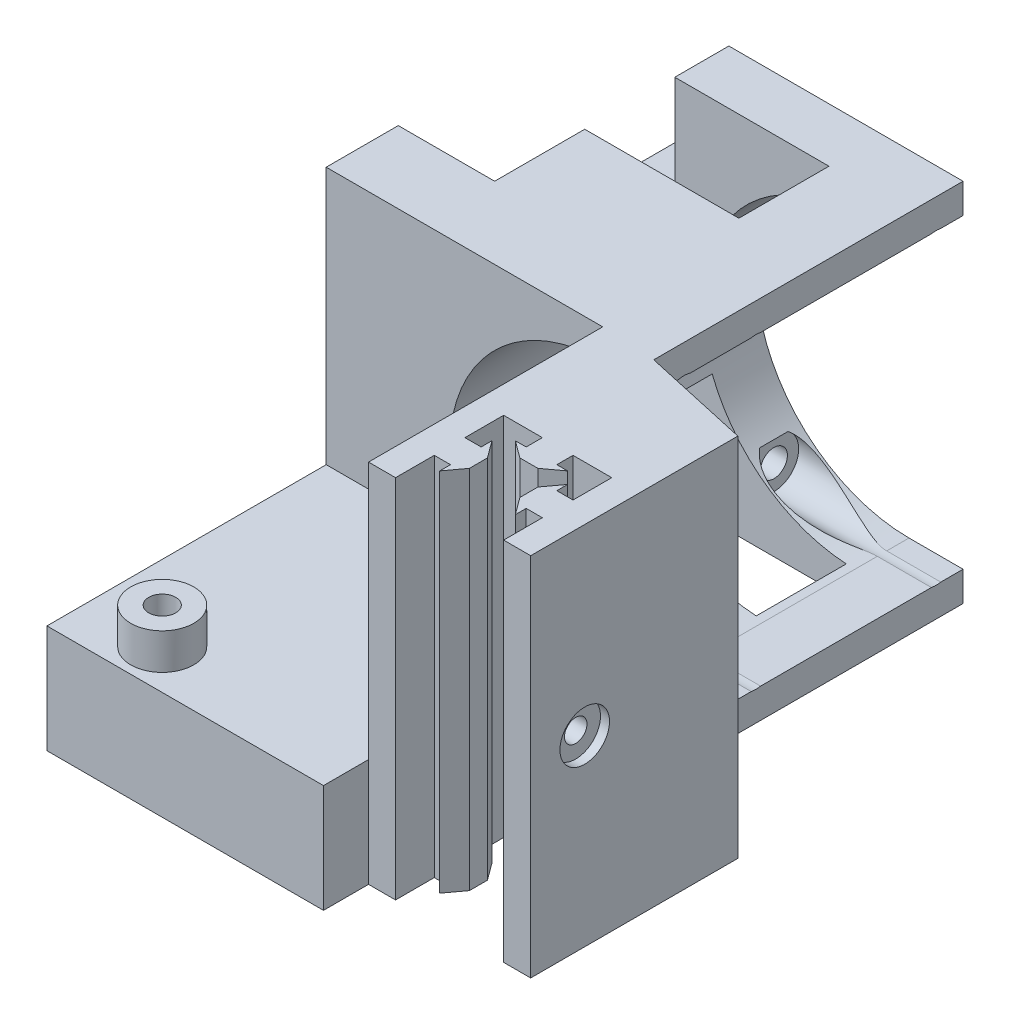
SolidWorks part; units mm, degrees
ref_plane "Plan de face" through (0, 0, 0) normal (0, 0, 1) x (1, 0, 0)
ref_plane "Plan de dessus" through (0, 0, 0) normal (0, 1, 0) x (1, 0, 0)
ref_plane "Plan de droite" through (0, 0, 0) normal (1, 0, 0) x (0, 0, -1)
ref_plane "Plan milieu" through (0, 0, -54) normal (0, 0, 1) x (1, 0, 0)
ref_axis "Axe1" through (0, 19.3307, 0) along (0, -1, 0)
ref_axis "Axe2" through (23.7847, 0, 0) along (-1, 0, 0)
ref_axis "Axe3" through (0, 0, -92.2336) along (0, 0, 1)
sketch "Esquisse8" plane through (0, 0, 0) normal (0, 1, 0) x (1, 0, 0)
  line L0 (-6, 1.7) -> (-4.2, 1.7)
  line L1 (0, -17.9979) -> (0, 17.9979) construction
  line L2 (-4.2, 1.7) -> (-4.2, 2.9)
  line L3 (-4.2, 2.9) -> (-2.8, 1)
  line L4 (-2.8, 1) -> (-2.8, -1)
  line L5 (-2.8, -1) -> (-4.2, -2.9)
  line L6 (-4.2, -2.9) -> (-4.2, -1.7)
  line L7 (-4.2, -1.7) -> (-6, -1.7)
  line L8 (-6, -1.7) -> (-6, -9)
  line L9 (-6, -9) -> (-9, -9)
  line L10 (-9, -9) -> (-9, 9)
  line L11 (-9, 9) -> (-6, 9)
  line L12 (-6, 9) -> (-6, 1.7)
  line L16 (23.7847, 0) -> (-17.9556, 0) construction
  point P14 (-2.8, 0)
  dimension "D1" = 1.8
  dimension "D2" = 3.2
  dimension "D3" = 18
  dimension "D4" = 2
  dimension "D5" = 1.2
  dimension "D7" = 3
  dimension "D8" = 3.4
  dimension "D9" = 6
extrude "Boss.-Extru.6" add sketch "Esquisse8" along normal mid plane 40.6 separate body
pattern_circular "Répétition circulaire3" count 3 every 90 about axis through (0, 19.3307, 0) along (0, -1, 0) of bodies 117
sketch "Esquisse9" plane through (0, 20.3, 0) normal (0, 1, 0) x (1, 0, 0)
  line L0 (9, -9) -> (9, 9) construction
  line L1 (-9, -9) -> (9, -9)
  line L2 (-9, -9) -> (-9, -6)
  line L3 (-9, -6) -> (9, -6)
  line L4 (9, -9) -> (9, -6)
  dimension "D1" = 3
extrude "Enlèv. mat.-Extru.1" cut sketch "Esquisse9" against normal through all
sketch "Esquisse10" plane through (0, 0, -9) normal (0, 0, -1) x (-1, 0, 0)
  line L0 (6, -20.3) -> (9, -20.3) construction
  line L1 (9, 20.3) -> (3, 20.3)
  line L2 (9, 20.3) -> (9, -20.3)
  line L3 (9, -20.3) -> (3, -20.3)
  line L4 (3, 20.3) -> (3, -20.3)
  line L5 (-9, -20.3) -> (9, -20.3) construction
  dimension "D1" = 6
extrude "Boss.-Extru.7" add sketch "Esquisse10" along normal up to surface (45 mm away) up to plane "Plan milieu"
sketch "Esquisse13" plane through (0, -20.3, 0) normal (0, -1, 0) x (-1, 0, 0)
  line L0 (9, 21) -> (-9, 17)
  line L1 (9, 54) -> (9, -6) construction
  line L2 (9, 21) -> (9, 9)
  line L3 (9, 9) -> (-9, 9)
  line L4 (-9, 6) -> (-9, 9) construction
  line L5 (-9, 17) -> (-9, 9)
  line L6 (9, 54) -> (9, -6) construction
  dimension "D1" = 12
  dimension "D2" = 8
extrude "Boss.-Extru.8" add sketch "Esquisse13" against normal up to surface (40.6 mm away) up to face at (-1.9333, 20.3, -7.6208)
sketch "Esquisse15" plane through (9, 0, 0) normal (1, 0, 0) x (0, 0, -1)
  line L0 (-6, -20.3) -> (-6, 20.3) construction
  line L2 (0, 19.3307) -> (0, -16.6651) construction
  circle A0 centre (0, 0) radius 1.25
  point P2 (-6, 0)
  dimension "D1" = 2.5
extrude "Enlèv. mat.-Extru.3" cut sketch "Esquisse15" against normal up to next
sketch "Esquisse19" plane through (9, 0, 0) normal (1, 0, 0) x (0, 0, -1)
  circle A0 centre (0, 0) radius 2.75
  circle A1 centre (0, 0) radius 1.25 construction
  dimension "D1" = 5.5
extrude "Enlèv. mat.-Extru.5" cut sketch "Esquisse19" against normal blind 1
sketch "Esquisse20" plane through (-9, 0, 0) normal (-1, 0, 0) x (0, 0, 1)
  line L0 (6, -20.3) -> (-54, -20.3) construction
  line L1 (-20, -20.3) -> (11, -20.3)
  line L2 (-20, -20.3) -> (-20, -8.3)
  line L3 (-20, -8.3) -> (11, -8.3)
  line L4 (11, -20.3) -> (11, -8.3)
  line L5 (6, -20.3) -> (6, 20.3) construction
  dimension "D1" = 31
  dimension "D2" = 12
  dimension "D3" = 5
extrude "Boss.-Extru.9" add sketch "Esquisse20" along normal blind 30.7
sketch "Esquisse21" plane through (0, -8.3, 0) normal (0, 1, 0) x (1, 0, 0)
  line L0 (-39.7, -11) -> (-39.7, 20) construction
  line L1 (-39.7, -11) -> (-9, -11) construction
  line L2 (-9, -6) -> (-9, 20) construction
  line L3 (-39.7, 20) -> (-9, 20) construction
  circle A0 centre (-31.3, -6.6) radius 3.5
  circle A1 centre (-13, 16) radius 3.5
  dimension "D1" = 7
  dimension "D4" = 4
  dimension "D2" = 8.4
  dimension "D3" = 4.4
  dimension "D5" = 4
extrude "Boss.-Extru.10" add sketch "Esquisse21" along normal blind 4
sketch "Esquisse22" plane through (0, -4.3, 0) normal (0, 1, 0) x (1, 0, 0)
  circle A0 centre (-13, 16) radius 1.5
  circle A1 centre (-13, 16) radius 3.5 construction
  circle A2 centre (-31.3, -6.6) radius 1.5
  dimension "D1" = 3
extrude "Enlèv. mat.-Extru.6" cut sketch "Esquisse22" against normal through all
sketch "Esquisse23" plane through (0, 0, -20) normal (0, 0, -1) x (-1, 0, 0)
  line L0 (39.7, -20.3) -> (9, -20.3) construction
  line L1 (29, -20.3) -> (5, -20.3)
  line L2 (29, -20.3) -> (29, 20.3)
  line L3 (29, 20.3) -> (5, 20.3)
  line L4 (5, -20.3) -> (5, 20.3)
  line L5 (9, -20.3) -> (9, 20.3) construction
  line L6 (9, 20.3) -> (3, 20.3) construction
  dimension "D1" = 24
  dimension "D2" = 4
extrude "Boss.-Extru.11" add sketch "Esquisse23" along normal blind 34
ref_plane "Plan1" through (9, 0, 0) normal (1, 0, 0) x (0, 0, -1)
ref_plane "Plan2" through (-9, 0, 0) normal (-1, 0, 0) x (0, 0, 1)
ref_plane "Plan3" through (-21, 0, 0) normal (-1, 0, 0) x (0, 0, 1)
sketch "Esquisse24" plane through (0, 0, -54) normal (0, 0, 1) x (1, 0, 0)
  line L0 (15.0486, 0) -> (-15.0486, 0) construction
  line L1 (-9, 17) -> (11, 17)
  line L2 (11, 17) -> (11, -17)
  line L3 (11, -17) -> (-9, -17)
  line L4 (-9, 24.9234) -> (-9, -24.9234) construction
  arc A1 (-9, 17) -> (-9, -17) centre (-9, 0) ccw
  dimension "D2" = 17
  dimension "D3" = 20
extrude "Enlèv. mat.-Extru.7" cut sketch "Esquisse24" along normal up to surface (34 mm away) up to face at (-19, 6, -20)
sketch "Esquisse25" plane through (-29, 0, 0) normal (-1, 0, 0) x (0, 0, 1)
  line L0 (-54, 20.3) -> (-20, 20.3) construction
  line L1 (-28, -20.3) -> (-20, -20.3)
  line L2 (-28, -20.3) -> (-28, 20.3)
  line L3 (-28, 20.3) -> (-20, 20.3)
  line L4 (-20, -20.3) -> (-20, 20.3)
  line L5 (-54, -20.3) -> (-20, -20.3) construction
  line L6 (-20, -8.3) -> (-20, 20.3) construction
  dimension "D1" = 8
extrude "Boss.-Extru.16" add sketch "Esquisse25" along normal up to surface (10.7 mm away) up to face at (-39.7, -14.3, -4.5)
sketch "Esquisse26" plane through (-29, 0, 0) normal (-1, 0, 0) x (0, 0, 1)
  line L0 (-54, 20.3) -> (-28, 20.3) construction
  line L1 (-28, 20.3) -> (-28, -20.3) construction
  circle A0 centre (-31, 14.3) radius 1.5
  dimension "D1" = 3
  dimension "D2" = 6
  dimension "D3" = 3
extrude "Enlèv. mat.-Extru.8" cut sketch "Esquisse26" against normal through all
sketch "Esquisse29" plane through (-21, 0, 0) normal (-1, 0, 0) x (0, 0, 1)
  circle A0 centre (-31, 14.3) radius 2.75
  circle A1 centre (-31, 14.3) radius 1.5 construction
  dimension "D1" = 5.5
extrude "Enlèv. mat.-Extru.13" cut sketch "Esquisse29" against normal through all
pattern_linear "Répétition linéaire1" count 2 spacing 20 along (0, 0, -1) of "Enlèv. mat.-Extru.8", "Enlèv. mat.-Extru.13"
mirror "Symétrie2" about plane through (0, 0, 0) normal (0, 1, 0) of "Répétition linéaire1"
sketch "Esquisse28" plane through (-29, 0, 0) normal (-1, 0, 0) x (0, 0, 1)
  line L0 (-28, 20.3) -> (-28, -20.3) construction
  line L1 (-28, 10) -> (-54, 10)
  line L2 (-28, 10) -> (-28, -10)
  line L3 (-28, -10) -> (-54, -10)
  line L4 (-54, 10) -> (-54, -10)
  line L5 (-54, -20.3) -> (-54, 20.3) construction
  line L6 (15.0486, 0) -> (-15.0486, 0) construction
  point P8 (-28, 0)
  dimension "D1" = 20
extrude "Boss.-Extru.17" add sketch "Esquisse28" along normal blind 4
sketch "Esquisse30" plane through (-33, 0, 0) normal (-1, 0, 0) x (0, 0, 1)
  line L0 (15.0486, 0) -> (-15.0486, 0) construction
  line L1 (-28, -20.3) -> (-28, 20.3) construction
  circle A0 centre (-31, 0) radius 1.5
  circle A1 centre (-31, 14.3) radius 1.5 construction
  dimension "D1" = 3
extrude "Enlèv. mat.-Extru.14" cut sketch "Esquisse30" against normal through all
pattern_linear "Répétition linéaire2" count 2 spacing 20 along (0, 0, -1) of "Enlèv. mat.-Extru.14"
sketch "Esquisse31" plane through (-29, 0, 0) normal (-1, 0, 0) x (0, 0, 1)
  circle A0 centre (-31, 0) radius 2.8
  dimension "D1" = 5.6
extrude "Enlèv. mat.-Extru.15" cut sketch "Esquisse31" against normal through all
ref_plane "Plan7" through (0, 0, -48) normal (0, 0, 1) x (1, 0, 0)
sketch "Esquisse34" plane through (0, 0, -48) normal (0, 0, 1) x (1, 0, 0)
  line L0 (-26.295, -5.3147) -> (-36.295, -22.6353)
  line L1 (-26.295, -5.3147) -> (-9, -15.3)
  line L2 (-13.235, -22.6353) -> (-9, -15.3)
  line L3 (-9, 24.9234) -> (-9, -24.9234) construction
  line L5 (-36.295, -22.6353) -> (-13.235, -22.6353)
  line L7 (-29, -20.3) -> (-3, -20.3) construction
  dimension "D1" = 20
  dimension "D2" = 60
  dimension "D4" = 5
extrude "Enlèv. mat.-Extru.20" cut sketch "Esquisse34" along normal blind 10
sketch "Esquisse35" plane through (-39.7, 0, 0) normal (-1, 0, 0) x (0, 0, 1)
  line L1 (-28, -20.3) -> (-28, 20.3) construction
  line L2 (-28, -20.3) -> (11, -20.3) construction
  circle A0 centre (-23, -14.3) radius 1.25
  dimension "D1" = 2.5
  dimension "D2" = 5
  dimension "D3" = 6
extrude "Enlèv. mat.-Extru.22" cut sketch "Esquisse35" against normal blind 20
sketch "Esquisse36" plane through (-29, 0, 0) normal (-1, 0, 0) x (0, 0, 1)
  circle A0 centre (-23, -14.3) radius 2.8
  circle A1 centre (-23, -14.3) radius 1.25 construction
  dimension "D1" = 5.6
extrude "Enlèv. mat.-Extru.23" cut sketch "Esquisse36" against normal through all
pattern_linear "Répétition linéaire4" count 3 spacing 12 along (0, 0, 1) of "Enlèv. mat.-Extru.22"
mirror "Symétrie9" about plane through (0, 0, 0) normal (0, 1, 0) of "Enlèv. mat.-Extru.20", "Enlèv. mat.-Extru.23", "Enlèv. mat.-Extru.22"
